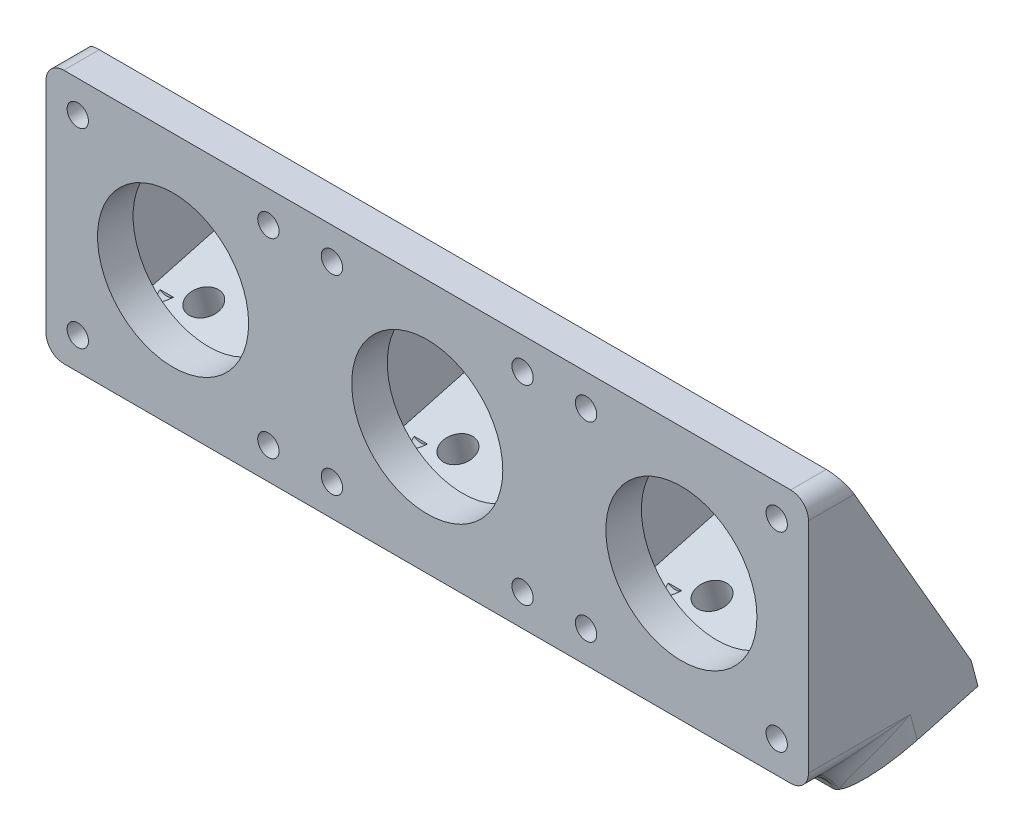
SolidWorks part; units mm, degrees
ref_plane "Front Plane" through (0, 0, 0) normal (0, 0, 1) x (1, 0, 0)
ref_plane "Top Plane" through (0, 0, 0) normal (0, 1, 0) x (1, 0, 0)
ref_plane "Right Plane" through (0, 0, 0) normal (1, 0, 0) x (0, 0, -1)
sketch "Sketch1" plane through (0, 0, 0) normal (0, 0, 1) x (1, 0, 0)
  line L0 (-28.6, 0) -> (16.7561, 45.3561) construction
  line L1 (-42.9, -14.3) -> (42.9, -14.3)
  line L2 (-42.9, -14.3) -> (-42.9, 14.3)
  line L3 (-42.9, 14.3) -> (42.9, 14.3)
  line L4 (42.9, -14.3) -> (42.9, 14.3)
  line L7 (-14.3, 14.3) -> (71.5, 14.3) [skipped]
  line L8 (14.3, 14.3) -> (100.1, 14.3) [skipped]
  circle A0 centre (-28.6, 0) radius 8.5
  circle A1 centre (0, 0) radius 8.5
  circle A2 centre (28.6, 0) radius 8.5
  circle A3 centre (-17.875, 10.725) radius 1.2
  circle A4 centre (-17.875, -10.725) radius 1.2
  circle A5 centre (-39.325, -10.725) radius 1.2
  circle A6 centre (-39.325, 10.725) radius 1.2
  circle A7 centre (-10.725, 10.725) radius 1.2
  circle A8 centre (10.725, 10.725) radius 1.2
  circle A9 centre (10.725, -10.725) radius 1.2
  circle A10 centre (-10.725, -10.725) radius 1.2
  circle A11 centre (17.875, 10.725) radius 1.2
  circle A12 centre (39.325, 10.725) radius 1.2
  circle A13 centre (39.325, -10.725) radius 1.2
  circle A14 centre (17.875, -10.725) radius 1.2
  point P11 (0, -14.3)
  point P12 (-42.9, 0)
  point P26 (-28.6, 0)
  dimension "D3" = 28.6
  dimension "D5" = 17
  dimension "D6" = 2.4
  dimension "D1" = 28.6
  dimension "D2" = 85.8
  dimension "D4" = 28.6
  dimension "D7" = 10.725
  dimension "D8" = 45
  dimension "D10" = 3
  dimension "D9" = 4
extrude "Boss-Extrude1" add sketch "Sketch1" along normal blind 4
sketch "Sketch2" plane through (42.9, 0, 0) normal (1, 0, 0) x (0, 0, -1)
  line L0 (0, -14.3) -> (14.3, -10.4683)
  line L1 (14.3, -10.4683) -> (0, 14.3)
  line L2 (0, 14.3) -> (0, -14.3)
  dimension "D1" = 75
  dimension "D2" = 75
extrude "Boss-Extrude2" add sketch "Sketch2" against normal blind 2
pattern_linear "LPattern1" count 4 spacing 27.9333 along (-1, 0, 0) of "Boss-Extrude2"
sketch "Sketch3" plane through (40.9, 0, 0) normal (-1, 0, 0) x (0, 0, 1)
  line L0 (0, -14.3) -> (-14.3, -10.4683)
  line L1 (-14.3, -10.4683) -> (-13.7824, -9.5718)
  line L2 (-14.3, -10.4683) -> (0, 14.3) construction
  line L3 (-13.7824, -9.5718) -> (0, -13.2647)
  line L4 (0, 14.3) -> (0, -14.3) construction
  line L5 (0, -13.2647) -> (0, -14.3)
  dimension "D1" = 1
extrude "Boss-Extrude5" add sketch "Sketch3" along normal up to surface (81.8 mm away) up to face at (-40.9, -3.4894, -4.7667)
sketch "Sketch4" plane through (0, 0, 4) normal (0, 0, 1) x (1, 0, 0)
  circle A0 centre (-39.325, -10.725) radius 1.2 construction
  circle A1 centre (-17.875, -10.725) radius 1.2 construction
  circle A2 centre (-10.725, -10.725) radius 1.2 construction
  circle A3 centre (10.725, -10.725) radius 1.2 construction
  circle A4 centre (17.875, -10.725) radius 1.2 construction
  circle A5 centre (39.325, -10.725) radius 1.2 construction
  circle A6 centre (-39.325, -10.725) radius 1.2
  circle A7 centre (-17.875, -10.725) radius 1.2
  circle A8 centre (-10.725, -10.725) radius 1.2
  circle A9 centre (10.725, -10.725) radius 1.2
  circle A10 centre (17.875, -10.725) radius 1.2
  circle A11 centre (39.325, -10.725) radius 1.2
extrude "Cut-Extrude1" cut sketch "Sketch4" against normal blind 10
fillet "Fillet1" radius 2 4 edges at (42.9, 14.3, 2) (42.9, -14.3, 2) (-42.9, -14.3, 2) (-42.9, 14.3, 2)
sketch "Sketch9" plane through (0, -13.3421, -3.575) normal (0, -0.9659, -0.2588) x (1, 0, 0)
  line L4 (42.9, -11.1033) -> (42.9, -4.0263)
  line L5 (40.9, 3.7011) -> (-40.9, 3.7011)
  line L6 (-42.9, -4.0263) -> (-42.9, -11.1033)
  line L7 (-42.9, -11.1033) -> (42.9, -11.1033)
  line L8 (42.9, -11.1033) -> (42.9, -4.0263)
  line L9 (40.9, 3.7011) -> (-40.9, 3.7011)
  line L10 (-42.9, -4.0263) -> (-42.9, -11.1033)
  line L11 (-42.9, -11.1033) -> (42.9, -11.1033)
  ellipse E2 centre (40.9, -4.0263) end of major axis (40.9, -11.7537) minor radius 2 (42.9, -4.0263) -> (40.9, 3.7011) ccw
  ellipse E3 centre (-40.9, -4.0263) end of major axis (-40.9, -11.7537) minor radius 2 (-40.9, 3.7011) -> (-42.9, -4.0263) ccw
  ellipse E4 centre (40.9, -4.0263) end of major axis (40.9, -11.7537) minor radius 2 (42.9, -4.0263) -> (40.9, 3.7011) ccw
  ellipse E5 centre (-40.9, -4.0263) end of major axis (-40.9, -11.7537) minor radius 2 (-40.9, 3.7011) -> (-42.9, -4.0263) ccw
  dimension "D1" = 0
extrude "Boss-Extrude6" add sketch "Sketch9" along normal blind 3
sketch "Sketch8" plane through (0, -12.3762, -3.3162) normal (0, 0.9659, 0.2588) x (1, 0, 0)
  line L0 (0, 0) -> (0, 50000) construction
  line L1 (-10.762, 3.7627) -> (-9.131, 6.5877)
  line L2 (10.762, 3.7627) -> (9.131, 6.5877)
  line L3 (9.131, 6.5877) -> (5.869, 6.5877)
  line L4 (5.869, 6.5877) -> (4.238, 3.7627)
  line L5 (4.238, 3.7627) -> (5.869, 0.9377)
  line L6 (5.869, 0.9377) -> (9.131, 0.9377)
  line L7 (9.131, 0.9377) -> (10.762, 3.7627)
  line L8 (-9.131, 6.5877) -> (-5.869, 6.5877)
  line L9 (-5.869, 6.5877) -> (-4.238, 3.7627)
  line L10 (-4.238, 3.7627) -> (-5.869, 0.9377)
  line L11 (-5.869, 0.9377) -> (-9.131, 0.9377)
  line L12 (-9.131, 0.9377) -> (-10.762, 3.7627)
  circle A0 centre (7.5, 3.7627) radius 1.7
  circle A1 centre (-7.5, 3.7627) radius 1.7
  circle A2 centre (7.5, 3.7627) radius 2.825 construction
  dimension "D1" = 3.4
  dimension "D3" = 5.65
  dimension "D2" = 15
extrude "Cut-Extrude4" cut sketch "Sketch8" against normal through all contours A0 | A1 region at (7.5, -11.4023, -6.9507) region at (-7.5, -11.4023, -6.9507)
pattern_linear "LPattern2" count 2 spacing 28.6 along (1, 0, 0) count 2 spacing 28.6 along (-1, 0, 0) of "Cut-Extrude4"
fillet "Fillet2" radius 5 2 edges at (-42.3142, -13.7142, -2.1862) (42.3142, -13.7142, -2.1862)
